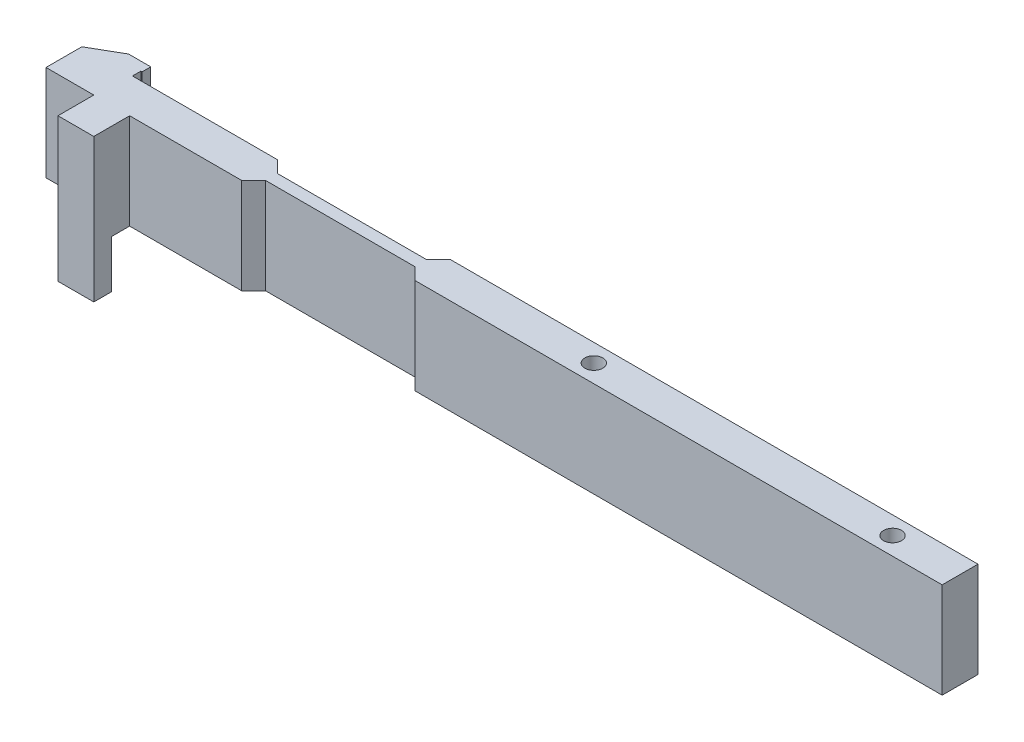
SolidWorks part; units mm, degrees
ref_plane "Спереди" through (0, 0, 0) normal (0, 0, 1) x (1, 0, 0)
ref_plane "Сверху" through (0, 0, 0) normal (0, 1, 0) x (1, 0, 0)
ref_plane "Справа" through (0, 0, 0) normal (1, 0, 0) x (0, 0, -1)
sketch "Эскиз1" plane through (0, 0, 0) normal (0, 1, 0) x (1, 0, 0)
  line L0 (0, 0) -> (-71.5259, 0)
  line L1 (-71.5259, 0) -> (-71.5259, 1.3965)
  line L2 (-71.5259, 1.3965) -> (-71.3259, 1.3965)
  line L3 (-71.3259, 1.3965) -> (-71.3259, 2.8586)
  line L4 (-71.3259, 2.8586) -> (-75.0357, 2.8586)
  line L5 (-75.0357, 2.8586) -> (-80, -0.0075)
  line L6 (-80, -0.0075) -> (-80, -6)
  line L7 (-80, -6) -> (70, -6)
  line L8 (70, -6) -> (70, 0)
  line L9 (70, 0) -> (0, 0)
  dimension "D1" = 150
  dimension "D2" = 30
  dimension "D3" = 0.2
  dimension "D4" = 6
  dimension "D5" = 70
extrude "Бобышка-Вытянуть1" add sketch "Эскиз1" along normal blind 16
sketch "Эскиз3" plane through (0, 16, 0) normal (0, 1, 0) x (1, 0, 0)
  line L0 (70, -3.0038) -> (-80, -3.0038) construction
  line L2 (-80, -0.0075) -> (-80, -6) construction
  line L3 (-47.2432, 0) -> (-45.2394, -2.0038)
  line L4 (70, 0) -> (-71.5259, 0) construction
  line L5 (-45.2394, -2.0038) -> (-20.2704, -2.0038)
  line L6 (-20.2704, -2.0038) -> (-18.2666, 0)
  line L7 (-47.2432, 0) -> (-18.2666, 0)
  line L8 (-47.2432, -6.0075) -> (-18.2666, -6.0075)
  line L9 (-20.2704, -4.0038) -> (-18.2666, -6.0075)
  line L10 (-45.2394, -4.0038) -> (-20.2704, -4.0038)
  line L11 (-47.2432, -6.0075) -> (-45.2394, -4.0038)
  circle A0 centre (8.6991, -3.0038) radius 1.5
  circle A1 centre (58.6991, -3.0038) radius 1.5
  dimension "D1" = 3
  dimension "D2" = 45
  dimension "D3" = 2
  dimension "D4" = 2
extrude "Вырез-Вытянуть1" cut sketch "Эскиз3" against normal through all
sketch "Эскиз4" plane through (0, 0, 0) normal (0, -1, 0) x (1, 0, 0)
  line L0 (-80, 6) -> (-47.2357, 6) construction
  line L1 (-80, 6) -> (-47.2357, 6) construction
  line L3 (-72, 12) -> (-66, 12)
  line L4 (-72, 12) -> (-72, 6)
  line L5 (-72, 6) -> (-66, 6)
  line L6 (-66, 12) -> (-66, 6)
  line L7 (-72, 12) -> (-66, 6) construction
  line L8 (-72, 6) -> (-66, 12) construction
  point P2 (-69, 9)
  dimension "D1" = 6
  dimension "D2" = 8
extrude "Бобышка-Вытянуть2" add sketch "Эскиз4" against normal up to surface (16 mm away) up to face at (58.6991, 16, 4.5038)
sketch "Эскиз5" plane through (0, 16, 0) normal (0, 1, 0) x (1, 0, 0)
  line L0 (-72, -12) -> (-72, -6)
  line L1 (-72, -6) -> (-69, -6)
  line L2 (-69, -6) -> (-66, -9)
  line L3 (-66, -12) -> (-66, -6) construction
  line L4 (-66, -9) -> (-66, -12)
  line L5 (-66, -12) -> (-72, -12)
  line L6 (-69, -12) -> (-69, -6) construction
extrude "Бобышка-Вытянуть3" [suppressed] add sketch "Эскиз5" along normal blind 8
extrude "Бобышка-Вытянуть4" add sketch "Эскиз5<2>" against normal blind 8 from surface starting at face at (58.6991, 0, 4.5038)
sketch "Эскиз5<2>" plane through (0, 16, 0) normal (0, 1, 0) x (1, 0, 0) same geometry as "Эскиз5"
